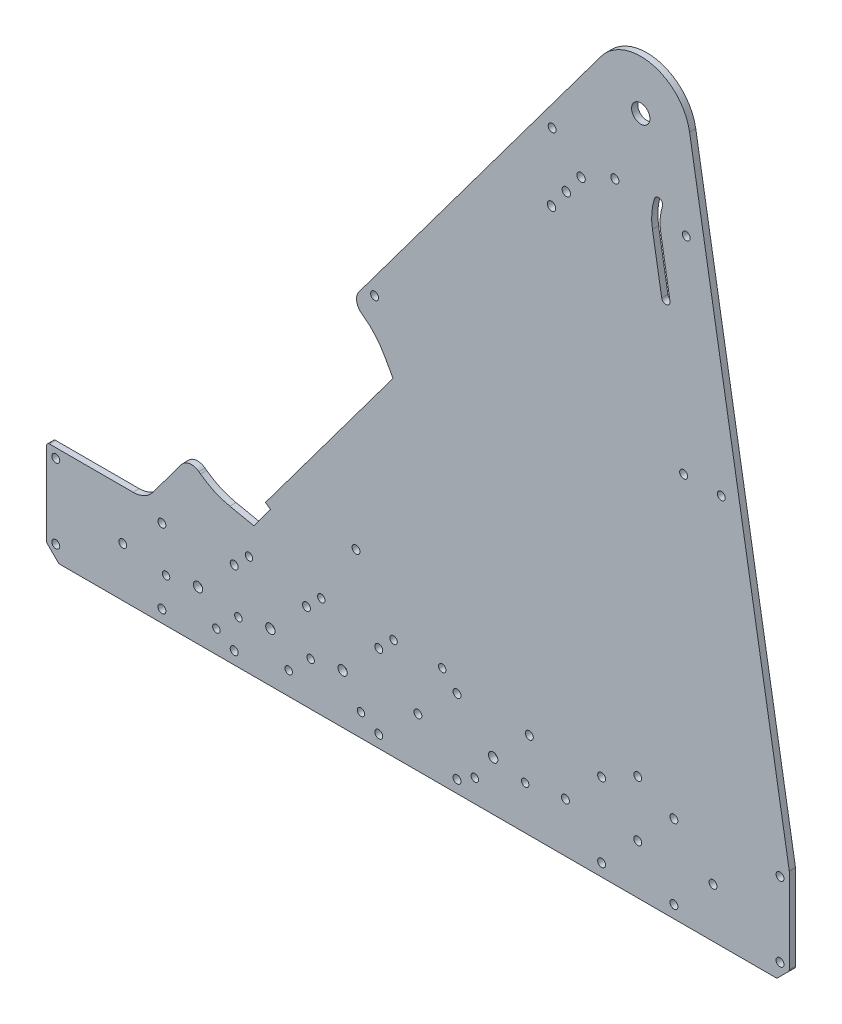
SolidWorks part; units mm, degrees
ref_plane "Front Plane" through (0, 0, 0) normal (0, 0, 1) x (1, 0, 0)
ref_plane "Top Plane" through (0, 0, 0) normal (0, 1, 0) x (1, 0, 0)
ref_plane "Right Plane" through (0, 0, 0) normal (1, 0, 0) x (0, 0, -1)
sketch "Sketch1" plane through (0, 0, 0) normal (0, 0, 1) x (1, 0, 0)
  line L1 (0, 0) -> (381, 0)
  line L2 (0, 0) -> (0, 50.8)
  line L4 (381, 0) -> (381, 50.8)
  line L5 (381, 50.8) -> (329.8448, 353.4827)
  line L6 (0, 50.8) -> (44.4242, 50.8)
  line L7 (54.6089, 55.913) -> (73.025, 80.6347)
  line L9 (112.3289, 80.2488) -> (177.7421, 168.0591)
  line L11 (156.4817, 192.6662) -> (284.4306, 364.4239)
  line L12 (112.3289, 80.2488) -> (114.875, 78.3521)
  line L13 (114.875, 78.3521) -> (106.3397, 66.8943)
  line L14 (156.4817, 192.6662) -> (169.2125, 183.1825)
  line L15 (169.2125, 183.1825) -> (177.7421, 168.0591)
  line L16 (73.025, 80.6347) -> (85.7559, 71.151)
  line L17 (85.7559, 71.151) -> (106.3397, 66.8943)
  line L18 (169.2125, 183.1825) -> (85.7559, 71.151) construction
  arc A0 (284.4306, 364.4239) -> (329.8448, 353.4827) centre (304.8, 349.25) cw
  arc A1 (44.4242, 50.8) -> (54.6089, 55.913) centre (44.4242, 63.5) ccw
  point P11 (50.8, 50.8)
  dimension "D4" = 349.25
  dimension "D7" = 12.7
  dimension "D5" = 25.4
  dimension "D1" = 50.8
  dimension "D2" = 381
  dimension "D3" = 76.2
  dimension "D6" = 50.8
  dimension "D8" = 123.825
  dimension "D9" = 139.7
  dimension "D10" = 15.875
  dimension "D11" = 31.75
  dimension "D12" = 73.025
  dimension "D13" = 3.175
  dimension "D14" = 14.2875
  dimension "D15" = 115
extrude "Boss-Extrude1" add sketch "Sketch1" along normal blind 3.175
sketch "Sketch2" plane through (0, 0, 3.175) normal (0, 0, 1) x (1, 0, 0)
  line L1 (190.5, 50.8) -> (190.5, 0) construction
  line L3 (0, 0) -> (381, 0) construction
  line L5 (0, 6.35) -> (0, 0)
  line L6 (0, 50.8) -> (0, 0) construction
  line L7 (0, 0) -> (6.35, 0)
  line L8 (6.35, 0) -> (0, 6.35)
  line L9 (381, 0) -> (374.65, 0)
  line L10 (374.65, 0) -> (381, 6.35)
  line L11 (381, 6.35) -> (381, 0)
  circle A19 centre (4.7625, 46.0375) radius 2.032
  circle A20 centre (4.7625, 7.9375) radius 2.032
  circle A21 centre (376.2375, 7.9375) radius 2.032
  circle A22 centre (376.2375, 46.0375) radius 2.032
  dimension "D21" = 6.35
  dimension "D27" = 4.064
  dimension "D4" = 46.0375
  dimension "D22" = 6.35
  dimension "D25" = 4.7625
  dimension "D28" = 7.9375
extrude "Cut-Extrude1" cut sketch "Sketch2" against normal up to next
sketch "Sketch5" plane through (0, 0, 3.175) normal (0, 0, 1) x (1, 0, 0)
  line L0 (151.892, 25.4) -> (229.108, 25.4) construction
  line L1 (229.108, 25.4) -> (341.884, 25.4) construction
  circle A0 centre (39.116, 25.4) radius 2.032
  circle A1 centre (59.182, 6.35) radius 2.032
  circle A2 centre (59.182, 44.45) radius 2.032
  circle A3 centre (96.266, 44.45) radius 2.032
  circle A4 centre (133.35, 44.45) radius 2.032
  circle A5 centre (170.434, 44.45) radius 2.032
  circle A6 centre (210.566, 44.45) radius 2.032
  circle A7 centre (210.566, 6.35) radius 2.032
  circle A8 centre (170.434, 6.35) radius 2.032
  circle A9 centre (247.65, 44.45) radius 2.032
  circle A10 centre (266.192, 25.4) radius 2.032
  circle A11 centre (39.116, 25.4) radius 2.286 construction
  circle A12 centre (59.182, 44.45) radius 1.905 construction
  circle A13 centre (59.182, 6.35) radius 1.905 construction
  circle A14 centre (96.266, 44.45) radius 1.905 construction
  circle A15 centre (133.35, 44.45) radius 1.905 construction
  circle A16 centre (170.434, 44.45) radius 1.905 construction
  circle A17 centre (170.434, 6.35) radius 2.159 construction
  circle A18 centre (210.566, 6.35) radius 2.159 construction
  circle A19 centre (210.566, 44.45) radius 1.905 construction
  circle A20 centre (247.65, 44.45) radius 1.905 construction
  circle A21 centre (266.192, 25.4) radius 2.286 construction
  circle A22 centre (77.724, 25.4) radius 2.3813
  circle A23 centre (114.808, 25.4) radius 2.3813
  circle A24 centre (151.892, 25.4) radius 2.3813
  circle A25 centre (229.108, 25.4) radius 2.3813
  circle A26 centre (190.5, 25.4) radius 2.032
  circle A28 centre (303.276, 25.4) radius 2.032
  circle A29 centre (341.884, 25.4) radius 2.032
  circle A30 centre (77.724, 25.4) radius 7.366 construction
  circle A31 centre (114.808, 25.4) radius 7.366 construction
  circle A32 centre (151.892, 25.4) radius 7.366 construction
  circle A33 centre (229.108, 25.4) radius 7.366 construction
  dimension "D1" = 4.064
  dimension "D2" = 4.7625
  dimension "D3" = 37.084
  dimension "D4" = 38.608
  dimension "D5" = 38.608
extrude "Cut-Extrude4" cut sketch "Sketch5" against normal through all
sketch "Sketch6" plane through (0, 0, 3.175) normal (0, 0, 1) x (1, 0, 0)
  line L0 (6.35, 0) -> (374.65, 0) construction
  line L1 (266.192, 25.4) -> (303.276, 25.4) construction
  line L2 (284.734, 6.35) -> (284.734, 44.45) construction
  line L3 (151.892, 25.4) -> (114.808, 25.4) construction
  line L4 (114.808, 25.4) -> (77.724, 25.4) construction
  circle A0 centre (284.734, 44.45) radius 2.032
  circle A1 centre (284.734, 6.35) radius 2.032
  circle A2 centre (321.818, 6.35) radius 2.032
  circle A3 centre (321.818, 44.45) radius 2.032
  circle A4 centre (96.266, 6.35) radius 2.032
  circle A6 centre (303.276, 53.975) radius 2.032
  arc A7 (304.329, 52.3875) -> (302.223, 52.3875) centre (303.276, 53.975) ccw construction
  point P8 (284.734, 25.4)
  point P9 (284.734, 25.4)
  point P18 (0, 0)
  point P28 (96.266, 25.4)
  dimension "D1" = 4.064
  dimension "D2" = 6.35
  dimension "D3" = 37.084
extrude "Cut-Extrude5" cut sketch "Sketch6" against normal through all
sketch "Sketch3" plane through (0, 0, 3.175) normal (0, 0, 1) x (1, 0, 0)
  line L0 (73.025, 80.6347) -> (54.6089, 55.913) construction
  line L1 (381, 6.35) -> (381, 50.8) construction
  line L2 (6.35, 0) -> (374.65, 0) construction
  line L3 (304.8, 349.25) -> (291.5148, 313.5413) construction
  line L4 (274.1929, 305.6133) -> (291.5148, 313.5413) construction
  line L5 (274.1929, 305.6133) -> (266.6059, 295.4286) construction
  line L6 (266.6059, 295.4286) -> (259.0189, 285.2439) construction
  line L7 (381, 50.8) -> (329.8448, 353.4827) construction
  line L9 (0, 50.8) -> (0, 6.35) construction
  line L14 (284.4306, 364.4239) -> (156.4817, 192.6662) construction
  line L15 (317.6782, 273.05) -> (310.9955, 312.5915) construction
  line L16 (315.5494, 272.6902) -> (310.8032, 300.7736)
  line L17 (319.8071, 273.4098) -> (315.0608, 301.4932)
  circle A0 centre (304.8, 349.25) radius 4.699
  circle A1 centre (168.275, 200.025) radius 2.032
  circle A2 centre (158.75, 82.55) radius 2.032
  circle A3 centre (291.5148, 313.5413) radius 2.0955
  circle A5 centre (274.1929, 305.6133) radius 2.159
  circle A6 centre (266.6059, 295.4286) radius 2.159
  circle A7 centre (259.0189, 285.2439) radius 2.159
  circle A8 centre (328.1309, 306.4656) radius 2.032
  circle A9 centre (346.12, 200.025) radius 2.032
  circle A12 centre (259.3534, 320.1311) radius 2.032
  circle A13 centre (326.7999, 200.025) radius 2.032
  arc A14 (315.0608, 301.4932) -> (315.9738, 313.6513) centre (340.1056, 305.7259) cw
  arc A19 (315.5494, 272.6902) -> (319.8071, 273.4098) centre (317.6782, 273.05) ccw
  arc A21 (315.9738, 313.6513) -> (311.8713, 314.9987) centre (313.9226, 314.325) ccw
  arc A22 (311.8713, 314.9987) -> (310.8032, 300.7736) centre (340.1056, 305.7259) ccw
  point P34 (312.6131, 324.0981)
  point P41 (313.3855, 298.45)
  dimension "D1" = 9.398
  dimension "D3" = 4.064
  dimension "D6" = 4.064
  dimension "D11" = 4.318
  dimension "D10" = 4.191
  dimension "D13" = 4.064
  dimension "D20" = 4.064
  dimension "D18" = 3.175
  dimension "D34" = 4.318
  dimension "D21" = 25.4
  dimension "D4" = 222.25
  dimension "D5" = 82.55
  dimension "D7" = 19.05
  dimension "D8" = 12.7
  dimension "D9" = 38.1
  dimension "D12" = 12.7
  dimension "D14" = 9.525
  dimension "D15" = 9.525
  dimension "D16" = 107.95
  dimension "D17" = 200.025
  dimension "D19" = 34.925
  dimension "D23" = 53.975
  dimension "D24" = 6.35
  dimension "D25" = 200.025
  dimension "D26" = 168.275
  dimension "D27" = 28.575
  dimension "D30" = 30
  dimension "D31" = 135
  dimension "D33" = 25.4
  dimension "D35" = 273.05
extrude "Cut-Extrude2" cut sketch "Sketch3" against normal through all
fillet "Fillet1" radius 1.5875 6 edges at (374.65, 0, 1.5875) (381, 6.35, 1.5875) (381, 50.8, 1.5875) (6.35, 0, 1.5875) (0, 6.35, 1.5875) (0, 50.8, 1.5875)
sketch "Sketch4" plane through (0, 0, 0) normal (0, 0, -1) x (-1, 0, 0)
  circle A0 centre (-61.3181, 22.2981) radius 1.905 construction
  circle A1 centre (-87.1313, 11.606) radius 1.905 construction
  circle A2 centre (-98.4021, 22.2981) radius 1.905 construction
  circle A3 centre (-124.2153, 11.606) radius 1.905 construction
  circle A4 centre (-135.4861, 22.2981) radius 1.905 construction
  circle A5 centre (-161.2993, 11.606) radius 1.905 construction
  circle A6 centre (-245.5139, 22.2981) radius 1.905 construction
  circle A7 centre (-219.7007, 11.606) radius 1.905 construction
  circle A8 centre (-202.982, 51.9684) radius 1.905 construction
  circle A9 centre (-178.018, 51.9684) radius 1.905 construction
  circle A10 centre (-140.934, 51.9684) radius 1.905 construction
  circle A11 centre (-103.85, 51.9684) radius 1.905 construction
  circle A12 centre (-61.3181, 22.2981) radius 1.905
  circle A13 centre (-87.1313, 11.606) radius 1.905
  circle A14 centre (-98.4021, 22.2981) radius 1.905
  circle A15 centre (-124.2153, 11.606) radius 1.905
  circle A16 centre (-135.4861, 22.2981) radius 1.905
  circle A17 centre (-161.2993, 11.606) radius 1.905
  circle A18 centre (-245.5139, 22.2981) radius 1.905
  circle A19 centre (-219.7007, 11.606) radius 1.905
  circle A20 centre (-202.982, 51.9684) radius 1.905
  circle A21 centre (-178.018, 51.9684) radius 1.905
  circle A22 centre (-140.934, 51.9684) radius 1.905
  circle A23 centre (-103.85, 51.9684) radius 1.905
extrude "Cut-Extrude3" cut sketch "Sketch4" against normal up to next
fillet "Fillet2" radius 38.1 2 edges at (85.7559, 71.151, 1.5875) (169.2125, 183.1825, 1.5875)
fillet "Fillet3" radius 6.35 2 edges at (73.025, 80.6347, 1.5875) (156.4817, 192.6662, 1.5875)
